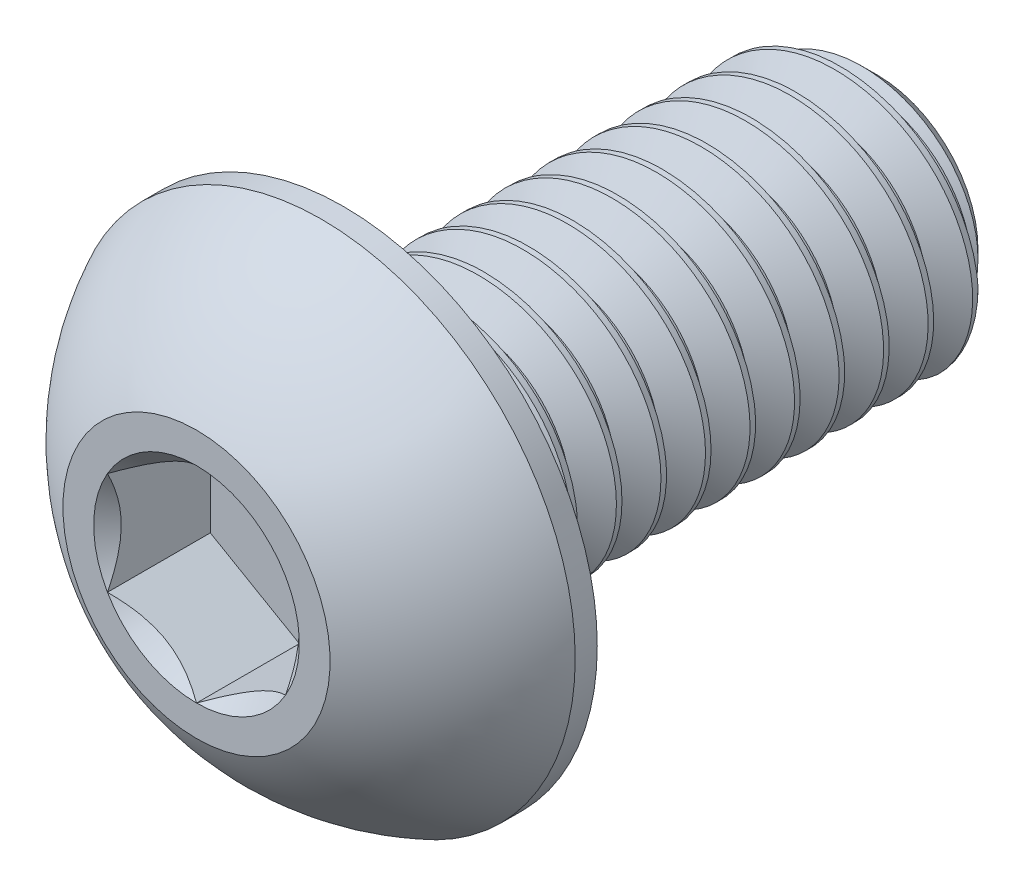
SolidWorks part; units mm, degrees
ref_plane "Front" through (0, 0, 0) normal (0, 0, 1) x (1, 0, 0)
ref_plane "Top" through (0, 0, 0) normal (0, 1, 0) x (1, 0, 0)
ref_plane "Right" through (0, 0, 0) normal (1, 0, 0) x (0, 0, -1)
sketch "Sketch1" plane through (0, 0, 0) normal (1, 0, 0) x (0, 0, -1)
  line L2 (1.65, 1.5) -> (7.65, 1.5)
  line L3 (7.65, 1.5) -> (7.65, 0)
  line L4 (7.65, 0) -> (1.65, 0)
  line L6 (1.4025, 2.85) -> (1.65, 2.85) construction
  line L7 (7.65, 1.5) -> (7.65, -1.5) construction
  line L8 (0, 0) -> (1.65, 0) construction
  line L9 (1.65, 2.85) -> (1.65, -2.85) construction
  line L11 (1.65, 1.5) -> (1.65, 0)
  line L13 (0, 1) -> (0, -1) construction
  line L14 (0, 1) -> (0, 1.5) construction
  arc A3 (0, 1.5) -> (1.4025, 2.85) centre (2.7948, 0) cw construction
  dimension "D1" = 0.2475
revolve "Revolve1" add sketch "Sketch1" angle 360 mid plane about L4
sketch "Sketch3" plane through (0, 0, -7.65) normal (0, 0, -1) x (-1, 0, 0)
  circle A0 centre (0, 0) radius 1.5
curve "Helix/Spiral1" pitch 0.5 height 6.5 radius 1.5 centre (0, 0, -7.65) axis (0, 0, 1) start towards (0, 1, 0)
sketch "Sketch2" plane through (0, 0, 0) normal (1, 0, 0) x (0, 0, -1)
  line L0 (7.65, 1.5) -> (8.0875, 1.5)
  line L1 (8.0875, 1.5) -> (7.9, 1.1752)
  line L2 (7.9, 1.1752) -> (7.8375, 1.1752)
  line L3 (7.8375, 1.1752) -> (7.65, 1.5)
  line L4 (7.7438, 1.3376) -> (7.9938, 1.3376) construction
  dimension "D1" = 60
  dimension "D2" = 0.0625
  dimension "D3" = 0.25
chamfer "Chamfer1" distance 0.375 angle 45 1 edges at (0, 1.5, -7.65)
sweep "Cut-Sweep1" cut profiles "Sketch2" path "Helix/Spiral1" align with end faces yes
sketch "Sketch7" plane through (0, 0, 0) normal (1, 0, 0) x (0, 0, -1)
  line L6 (1.4025, 2.85) -> (1.65, 2.85) construction
  line L8 (0, 0) -> (1.65, 0) construction
  line L11 (1.65, 2.85) -> (1.65, -2.85) construction
  line L12 (1.4025, 2.85) -> (1.65, 2.85)
  line L13 (0, 0) -> (1.65, 0)
  line L14 (0, 1) -> (0, -1) construction
  line L15 (1.65, 2.85) -> (1.65, 0)
  line L16 (0, 1.5) -> (0, 0)
  arc A2 (1.4025, 2.85) -> (0, 1.5) centre (2.7948, 0) ccw construction
  arc A3 (1.4025, 2.85) -> (0, 1.5) centre (2.7948, 0) ccw
revolve "Revolve2" add sketch "Sketch7" angle 360 mid plane about L13
sketch "Sketch5" plane through (0, 0, 0) normal (0, 0, 1) x (1, 0, 0)
  line L1 (1, -0.5774) -> (1, 0.5774)
  line L2 (1, 0.5774) -> (0, 1.1547)
  line L3 (0, 1.1547) -> (-1, 0.5774)
  line L4 (-1, 0.5774) -> (-1, -0.5774)
  line L5 (-1, -0.5774) -> (0, -1.1547)
  line L6 (0, -1.1547) -> (1, -0.5774)
  circle A0 centre (0, 0) radius 1 construction
extrude "Cut-Extrude2" cut sketch "Sketch5" against normal blind 1.155
sketch "Sketch6" plane through (0, 0, 0) normal (0, 0, 1) x (1, 0, 0)
  circle A0 centre (0, 0) radius 1.1547
extrude "Cut-Extrude3" cut sketch "Sketch6" against normal blind 1.155 draft 45
sketch "Sketch9" [suppressed] plane through (0, 0, -4.2164) normal (0, 0, 1) x (1, 0, 0)
  circle A2 centre (0, 0) radius 3.9687
extrude "Boss-Extrude2" [suppressed] add sketch "Sketch9" against normal offset from surface (9.525 mm away) 28.575 up to face at (0, 1.125, -7.65)
sketch "Sketch10" plane through (0, 0, 0) normal (1, 0, 0) x (0, 0, -1)
  line L0 (7.65, 1.5) -> (7.65, -1.5) construction
  point P0 (6.9, -1.5)
  dimension "D1" = 0.75
equation "\"D3@Helix/Spiral1\" = \"Lg@Sketch1\" + \"D4@Helix/Spiral1\""
equation "\"D2@Sketch2\" = \"D4@Helix/Spiral1\" * .125"
equation "\"D3@Sketch2\" = \"D4@Helix/Spiral1\" * .5"
equation "\"D1@Chamfer1\" = \"D4@Helix/Spiral1\" * .75"
equation "\"D1@Cut-Extrude2\" = \"Head Ht@Sketch1\" * .7"
equation "\"D1@Sketch1\" = \"Head Ht@Sketch1\" * .15"
equation "\"D1@Sketch10\" = \"D4@Helix/Spiral1\" * 1.5"
equation "\"D1@Cut-Extrude3\" = \"D1@Cut-Extrude2\""
